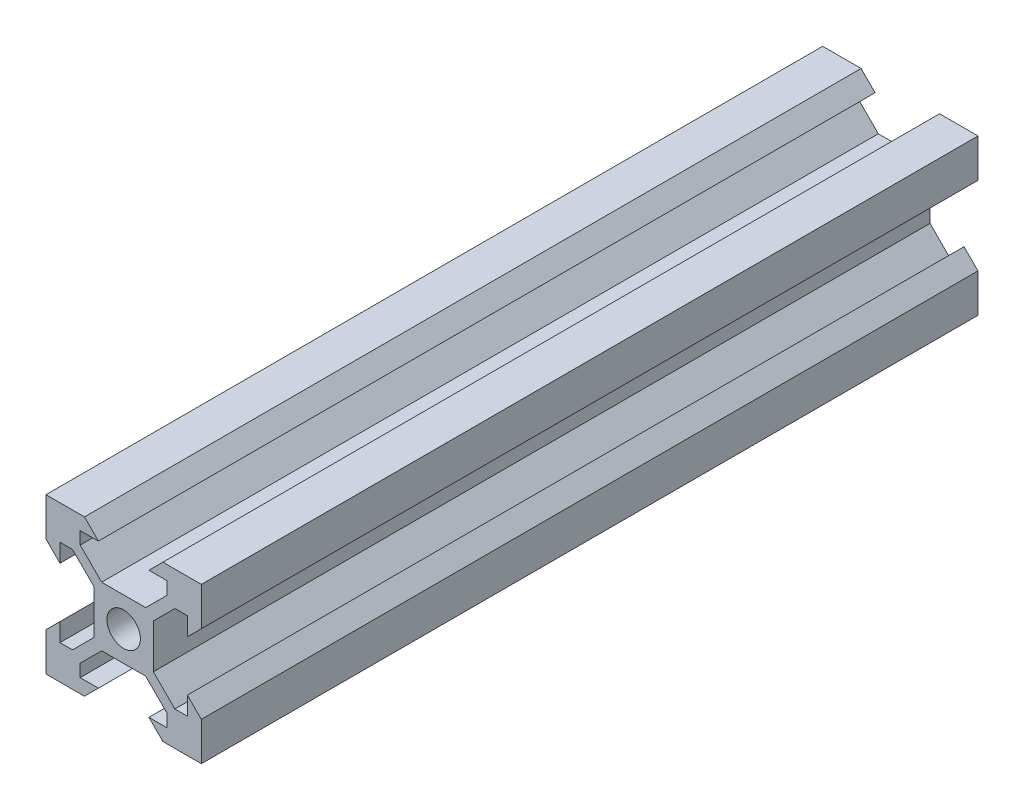
SolidWorks part; units mm, degrees
ref_plane "Alzado" through (0, 0, 0) normal (0, 0, 1) x (1, 0, 0)
ref_plane "Planta" through (0, 0, 0) normal (0, 1, 0) x (1, 0, 0)
ref_plane "Vista lateral" through (0, 0, 0) normal (1, 0, 0) x (0, 0, -1)
sketch "Croquis1" plane through (0, 0, 0) normal (0, 0, 1) x (1, 0, 0)
  line L0 (0, 0) -> (0, -20) construction
  line L2 (0, 0) -> (0, -0.5674)
  line L5 (6.175, -7.1649) -> (6.175, -12.8351)
  line L6 (7.1649, -13.825) -> (12.8351, -13.825)
  line L7 (13.825, -7.1649) -> (13.825, -12.8351)
  line L8 (7.1649, -6.175) -> (12.8351, -6.175)
  line L9 (6.175, -13.825) -> (13.825, -13.825) construction
  line L10 (13.825, -6.175) -> (13.825, -13.825) construction
  line L12 (10, -10) -> (32.1172, -10) construction
  line L13 (13.25, -18.2) -> (15.05, -20)
  line L14 (20, -20) -> (15.6, -20)
  line L15 (20, -20) -> (20, -15.6)
  line L16 (18.2, -15.6) -> (16.5899, -15.6)
  line L32 (15.6, -18.2) -> (15.6, -16.5899)
  line L33 (10, -10) -> (10, -23.2493) construction
  line L34 (4.4, -18.2) -> (4.4, -16.5899)
  line L35 (7.1649, -13.825) -> (4.4, -16.5899)
  line L36 (15.6, -18.2) -> (13.25, -18.2)
  line L38 (15.6, -20) -> (15.05, -20)
  line L40 (15.05, -20) -> (20, -20)
  line L41 (0, -20) -> (20, -20) construction
  line L42 (6.175, -12.8351) -> (3.4101, -15.6)
  line L43 (18.2, -13.25) -> (20, -15.05)
  line L44 (20, -20) -> (18.2, -20)
  line L45 (20, -20) -> (20, -15.05)
  line L48 (20, -15.05) -> (20, -20)
  line L49 (20, 0) -> (20, -20) construction
  line L50 (18.2, -15.6) -> (18.2, -13.25)
  line L51 (12.8351, -13.825) -> (15.6, -16.5899)
  line L52 (13.825, -12.8351) -> (16.5899, -15.6)
  line L53 (1.8, -15.6) -> (3.4101, -15.6)
  line L54 (1.8, -15.6) -> (1.8, -13.25)
  line L55 (1.8, -13.25) -> (0, -15.05)
  line L56 (0, 0) -> (20, 0) construction
  line L57 (0, -20) -> (0, -15.6)
  line L58 (0, -15.6) -> (0, -15.05)
  line L59 (0, -20) -> (4.4, -20)
  line L60 (0, -20) -> (4.95, -20)
  line L61 (6.75, -18.2) -> (4.95, -20)
  line L62 (4.4, -18.2) -> (6.75, -18.2)
  line L63 (1.8, -4.4) -> (3.4101, -4.4)
  line L64 (6.175, -7.1649) -> (3.4101, -4.4)
  line L65 (7.1649, -6.175) -> (4.4, -3.4101)
  line L66 (4.4, -1.8) -> (4.4, -3.4101)
  line L67 (4.4, -1.8) -> (6.75, -1.8)
  line L68 (6.75, -1.8) -> (4.95, 0)
  line L69 (0, 0) -> (4.4, 0)
  line L70 (4.4, 0) -> (4.95, 0)
  line L71 (0, 0) -> (0, -4.4)
  line L72 (0, 0) -> (0, -4.95)
  line L73 (1.8, -6.75) -> (0, -4.95)
  line L74 (1.8, -4.4) -> (1.8, -6.75)
  line L75 (15.6, -1.8) -> (15.6, -3.4101)
  line L76 (12.8351, -6.175) -> (15.6, -3.4101)
  line L77 (13.825, -7.1649) -> (16.5899, -4.4)
  line L78 (18.2, -4.4) -> (16.5899, -4.4)
  line L79 (18.2, -4.4) -> (18.2, -6.75)
  line L80 (18.2, -6.75) -> (20, -4.95)
  line L81 (20, 0) -> (20, -4.4)
  line L82 (20, -4.4) -> (20, -4.95)
  line L83 (20, 0) -> (15.6, 0)
  line L84 (20, 0) -> (15.05, 0)
  line L85 (13.25, -1.8) -> (15.05, 0)
  line L86 (15.6, -1.8) -> (13.25, -1.8)
  line L87 (6.175, -6.175) -> (13.825, -6.175) construction
  line L88 (6.175, -6.175) -> (6.175, -13.825) construction
  circle A0 centre (10, -10) radius 2.15
  point P69 (10, -10)
  dimension "D3" = 4.3
  dimension "D2" = 4
  dimension "D11" = 4.4
  dimension "D15" = 4.4
  dimension "D16" = 6.75
extrude "Saliente-Extruir2" add sketch "Croquis1" along normal blind 100 contours L86 L75 L76 L8 L65 L66 L67 L68 L70 L69 L2 L71 L72 L73 L74 L63 L64 L5 L42 L53 L54 L55 L58 L57 L59 L60 L61 L62 L34 L35 L6 L51 L32 L36 L13 L38 L40 L14 L15 L45 L43 L50 L16 L52 L7 L77 L78 L79 L80 L82 L81 region at (2.2, -0.2828, 0)
